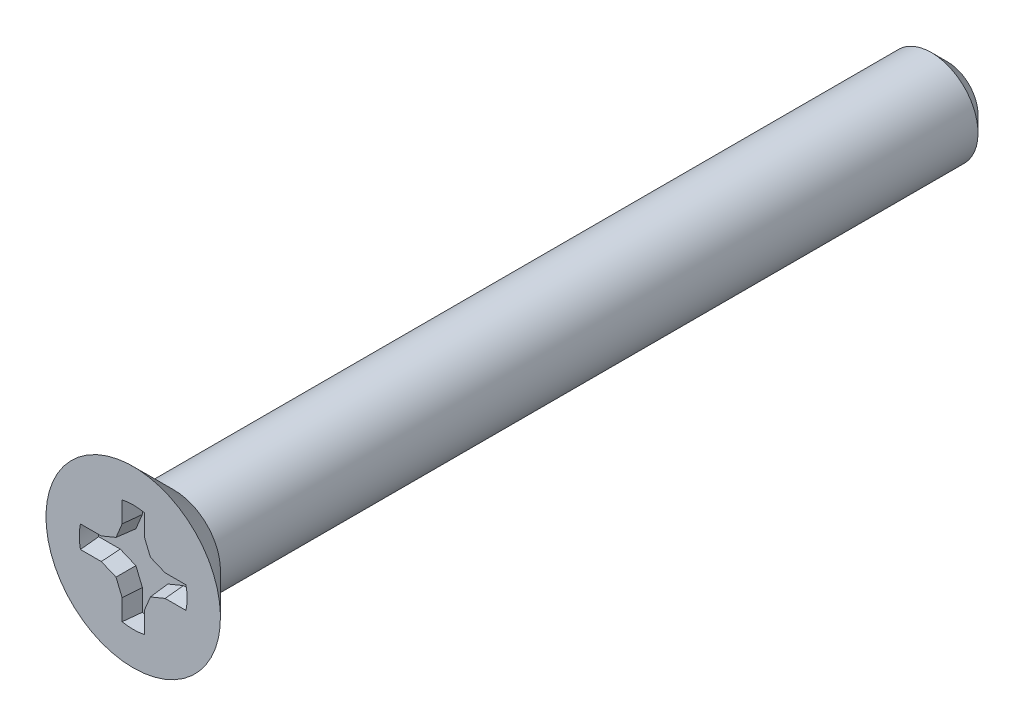
SolidWorks part; units mm, degrees
ref_plane "Front Plane" through (0, 0, 0) normal (0, 0, 1) x (1, 0, 0)
ref_plane "Top Plane" through (0, 0, 0) normal (0, 1, 0) x (1, 0, 0)
ref_plane "Right Plane" through (0, 0, 0) normal (1, 0, 0) x (0, 0, -1)
sketch "Sketch1" plane through (0, 0, 0) normal (1, 0, 0) x (0, 0, -1)
  line L0 (0, 0) -> (-0.96, 0) construction
  line L1 (-0.96, 1.5) -> (-0.96, -1.5) construction
  line L2 (-0.96, 1.5) -> (0, 0.54) construction
  line L3 (-0.96, -1.5) -> (0, -0.54) construction
  line L4 (0, 0.8) -> (0, -0.8) construction
  line L5 (0, 0) -> (13.04, 0) construction
  line L6 (0, 0.8) -> (0.35, 0.8) construction
  line L7 (0, 0.8) -> (-0.26, 0.8) construction
  line L8 (13.04, 0.54) -> (13.04, -0.54) construction
  point P6 (-0.96, 0)
  point P11 (0, 0)
  point P16 (-0.26, 0.8)
  point P17 (11.815, -0.8)
  point P20 (13.04, 0)
  point P21 (-0.48, 0)
  point P22 (11.815, -0.54)
  point P23 (13.04, -0.54)
  point P25 (13.04, 0.54)
  dimension "Head Height" = 0.96
  dimension "Head Diameter" = 3
  dimension "Countersink Angle" = 90
  dimension "Thread OD" = 1.6
  dimension "Length" = 14
  dimension "Thread Pitch" = 0.35
  dimension "D1" = 1.225
sketch "Sketch2" plane through (0, 0, 0) normal (0, 0, 1) x (1, 0, 0)
  line L0 (0.1905, 0.9271) -> (-0.1905, 0.9271) construction
  circle A0 centre (0, 0) radius 0.9271 construction
  point P3 (0, 0.9271)
  point P7 (0, 0.9271)
  dimension "Drive Dia" = 1.8542
  dimension "Drive Width" = 0.381
sketch "Sketch3" plane through (0, 0, 0) normal (1, 0, 0) x (0, 0, -1)
  line L0 (-0.96, 0) -> (-0.96, 1.5)
  line L1 (-0.96, 1.5) -> (-0.26, 0.8)
  line L2 (-0.96, 1.5) -> (0, 0.54) construction
  line L3 (0, 0.8) -> (0.35, 0.8) construction
  line L4 (-0.96, 0) -> (-0.26, 0)
  line L5 (0, 0) -> (-0.96, 0) construction
  line L6 (-0.26, 0) -> (-0.26, 0.8)
revolve "Revolve1" add sketch "Sketch3" angle 360 about L4
sketch "Sketch5" plane through (0, 0, 0) normal (1, 0, 0) x (0, 0, -1)
  line L0 (13.04, 0) -> (-0.26, 0)
  line L1 (0, 0) -> (13.04, 0) construction
  line L2 (-0.26, 0) -> (-0.26, 0.8)
  line L3 (-0.26, 0.8) -> (12.7635, 0.8)
  line L4 (12.7635, 0.8) -> (13.04, 0.5235)
  line L5 (13.04, 0.5235) -> (13.04, 0)
  line L6 (12.7635, 0.8) -> (13.04, 0.8) construction
  line L7 (13.04, 0.8) -> (13.04, 0.5235) construction
  line L8 (0, 0.8) -> (0.35, 0.8) construction
  line L9 (-0.26, -0.8) -> (-0.26, 0.8) construction
  dimension "D1" = 0.2765
revolve "Revolve2" add sketch "Sketch5" angle 360 about L0
sketch "Sketch4" plane through (0, 0, 0.96) normal (0, 0, 1) x (1, 0, 0)
  line L0 (0, 0) -> (0, 0.9271)
  line L1 (0, 0) -> (0.9271, 0)
  line L2 (0, 0) -> (0.5489, 0.5489) construction
  line L3 (0.1905, 0.9073) -> (0.1905, 0.5489)
  line L4 (0.1905, 0.5489) -> (0.1905, 0.1905) construction
  line L5 (0.5489, 0.1905) -> (0.1905, 0.1905) construction
  line L6 (0.9073, 0.1905) -> (0.5489, 0.1905)
  line L7 (0.1905, 0.5489) -> (0.2955, 0.2955)
  line L8 (0.2955, 0.2955) -> (0.5489, 0.1905)
  line L9 (0, 0.9271) -> (0, 1.5) construction
  line L10 (0, 1.5) -> (0, -1.5) construction
  circle A0 centre (0, 0) radius 0.9271 construction
  arc A1 (0, 0.9271) -> (0.1905, 0.9073) centre (0, 0) cw
  arc A2 (0.9271, 0) -> (0.9073, 0.1905) centre (0, 0) ccw
  arc A3 (0.5489, 0.1905) -> (0.1905, 0.5489) centre (0.5489, 0.5489) cw construction
  circle A4 centre (0, 0) radius 1.5 construction
  point P8 (0.2955, 0.2955)
  point P22 (0, -0.9271)
  point P23 (0, 0.9271)
  dimension "D1" = 0.5729
extrude "Cut-Extrude1" cut sketch "Sketch4" against normal blind 0.32 contours L1 A2 L6 L8 L7 L3 A1 L0 region at (0.0131, 0.4635, 0.96)
pattern_circular "CirPattern1" count 4 over 360 about axis through (0, 0, 0) along (0, 0, -1) of "Cut-Extrude1"
draft "Draft2" type of draft neutral plane draft angle 5 faces to draft 16 face at (-0.7281, 0.1905, 0.8) face at (-0.4222, 0.243, 0.8) face at (-0.243, 0.4222, 0.8) face at (-0.1905, 0.7281, 0.8) face at (0.1905, 0.7281, 0.8) face at (0.243, 0.4222, 0.8) face at (0.4222, 0.243, 0.8) face at (0.7281, 0.1905, 0.8) face at (0.7281, -0.1905, 0.8) face at (0.4222, -0.243, 0.8) face at (0.243, -0.4222, 0.8) face at (0.1905, -0.7281, 0.8) face at (-0.1905, -0.7281, 0.8) face at (-0.243, -0.4222, 0.8) face at (-0.4222, -0.243, 0.8) face at (-0.7281, -0.1905, 0.8) neutral plane through (0, 0, 0.96) neutral plane normal (0, 0, 1) parameters "D1"=5
ref_plane "Plane1" through (0, 0, 0.26) normal (0, 0, -1) x (-1, 0, 0)
split "Split1" trim tools "Plane1" bodies to split 107 105 resulting bodies 108 109
sketch "Sketch6" plane through (0, 0, -13.04) normal (0, 0, 1) x (1, 0, 0)
  circle A1 centre (0, 0) radius 0.8
  circle A2 centre (0, 0) radius 0.8
  dimension "D1" = 0
curve "Helix/Spiral1" pitch 0.35 height 14 turns 40
sketch "Sketch7" plane through (0, 0, 0) normal (1, 0, 0) x (0, 0, -1)
  line L0 (13.0181, 0.8379) -> (13.3681, 0.8379) construction
  line L1 (13.0181, 0.8379) -> (13.1931, 0.5348) construction
  line L2 (13.1931, 0.5348) -> (13.3681, 0.8379) construction
  line L3 (13.1712, 0.5727) -> (13.215, 0.5727) construction
  line L4 (13.04, 0.8) -> (13.3463, 0.8) construction
  line L5 (13.1931, 0.8) -> (13.1931, 0.8379) construction
  line L6 (13.1931, 0.5727) -> (13.1931, 0.5348) construction
  line L7 (13.1931, 0.8189) -> (13.0291, 0.8189) construction
  line L10 (13.215, 0.5727) -> (13.1712, 0.5727)
  line L11 (13.0291, 0.8189) -> (13.1712, 0.5727)
  line L12 (13.0291, 0.8189) -> (13.3572, 0.8189)
  line L13 (13.3572, 0.8189) -> (13.215, 0.5727)
  dimension "D1" = 0.35
  dimension "D2" = 0.0437
sweep "Cut-Sweep1" [suppressed] cut profiles "Sketch7" path "Helix/Spiral1"
combine bodies "Combine1" operation type add bodies to combine 109 108
ref_plane "Plane2" through (0, 0, 0.26) normal (0, 0, 1) x (1, 0, 0)
sketch "Sketch8" plane through (0, 0, 0.26) normal (0, 0, 1) x (1, 0, 0)
  circle A0 centre (0, 0) radius 0.8
extrude "Boss-Extrude1" add sketch "Sketch8" against normal up to vertex (0.26 mm away) draft 45 up to point (0, 0.54, 0)
equation "\"D1@Sketch5\" = \"Thread Pitch@Sketch1\" * .79"
equation "\"D4@Helix/Spiral1\" = \"Thread Pitch@Sketch1\""
equation "\"D3@Helix/Spiral1\"=\"Length@Sketch1\""
equation "\"D1@Sketch7\" = \"Thread Pitch@Sketch1\""
equation "\"D2@Sketch7\" = \"Thread Pitch@Sketch1\" / 8"
equation "\"D1@Sketch1\"=\"Thread Pitch@Sketch1\"*3.5"
equation "\"D1@Cut-Extrude1\"=\"Head Height@Sketch1\"/3"
